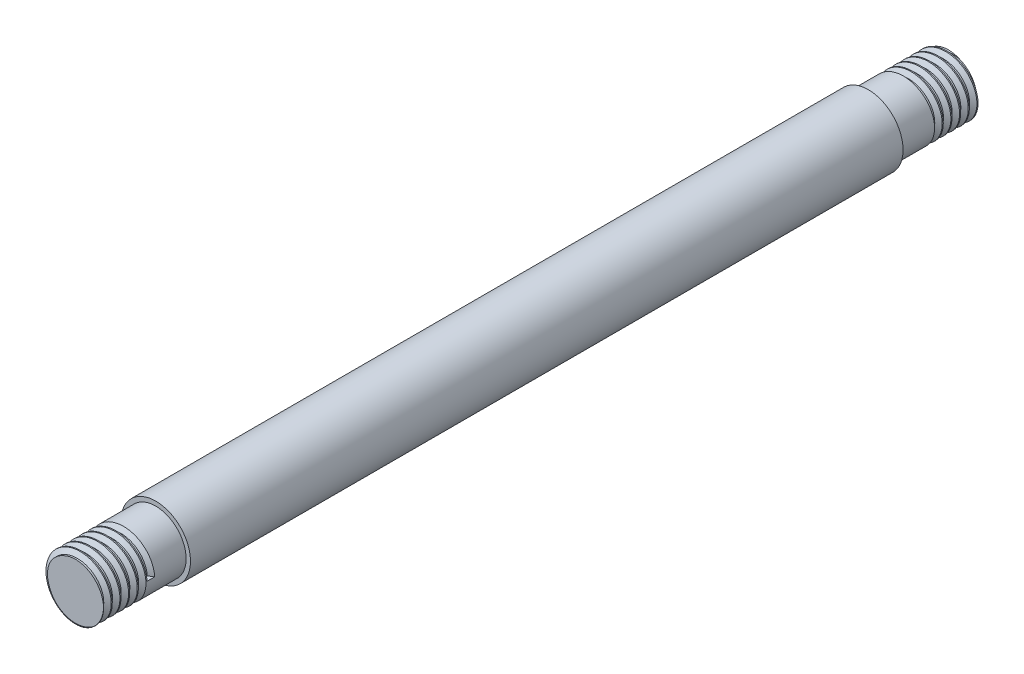
SolidWorks part; units mm, degrees
ref_plane "Front Plane" through (0, 0, 0) normal (0, 0, 1) x (1, 0, 0)
ref_plane "Top Plane" through (0, 0, 0) normal (0, 1, 0) x (1, 0, 0)
ref_plane "Right Plane" through (0, 0, 0) normal (1, 0, 0) x (0, 0, -1)
sketch "Sketch1" plane through (0, 0, 0) normal (1, 0, 0) x (0, 0, -1)
  line L27 (-69.0229, 0) -> (132.9771, 0)
  line L28 (132.9771, 0) -> (132.9771, -7)
  line L29 (132.9771, -7) -> (113.9771, -7)
  line L30 (113.9771, -7) -> (113.9771, -8)
  line L31 (113.9771, -8) -> (-50.0229, -8)
  line L32 (-50.0229, -8) -> (-50.0229, -7)
  line L33 (-50.0229, -7) -> (-69.0229, -7)
  line L34 (-69.0229, -7) -> (-69.0229, 0)
  dimension "D1" = 202
  dimension "D2" = 19
  dimension "D3" = 19
  dimension "D4" = 7
  dimension "D5" = 8
  dimension "D6" = 7
revolve "Revolve8" add sketch "Sketch1" angle 360 about L27
thread "Thread1" pitch 2 start angle 0, offset 3, length 10, pitch 2, diameter 14
ref_plane "Plane1" through (-7, 0, 72.0229) normal (0, -1, 0) x (-1, 0, 0)
sketch "Thread Profile1" plane through (-7, 0, 72.0229) normal (0, -1, 0) x (-1, 0, 0)
  line L0 (0, 0) -> (0, 2) construction
  line L11 (0, 0) -> (0, 1.75)
  line L12 (0, 1.75) -> (-1.0825, 1.125)
  line L13 (-1.0825, 1.125) -> (-1.0825, 0.625)
  line L15 (-1.0825, 0.625) -> (0, 0)
  line L17 (-1.0825, 0.875) -> (0, 0.875) construction
  point P2 (0, 0)
  dimension "Pitch" = 2
  dimension "Profile_Angle" = 60
  dimension "Profile_Land" = 0.5
  dimension "Profile_Height" = 1.0825
thread "Thread2" pitch 2 profile "Thread Profile2" start angle 0, offset 3, length 10, pitch 2, diameter 14
ref_plane "Plane2" through (7, 0, -135.9771) normal (0, -1, 0) x (1, 0, 0)
sketch "Thread Profile2" plane through (7, 0, -135.9771) normal (0, -1, 0) x (1, 0, 0)
  line L0 (0, 0) -> (0, 2) construction
  line L11 (0, 0) -> (0, 1.75)
  line L12 (0, 1.75) -> (-1.0825, 1.125)
  line L13 (-1.0825, 1.125) -> (-1.0825, 0.625)
  line L15 (-1.0825, 0.625) -> (0, 0)
  line L17 (-1.0825, 0.875) -> (0, 0.875) construction
  point P2 (0, 0)
  dimension "Pitch" = 2
  dimension "Profile_Angle" = 60
  dimension "Profile_Land" = 0.5
  dimension "Profile_Height" = 1.0825
